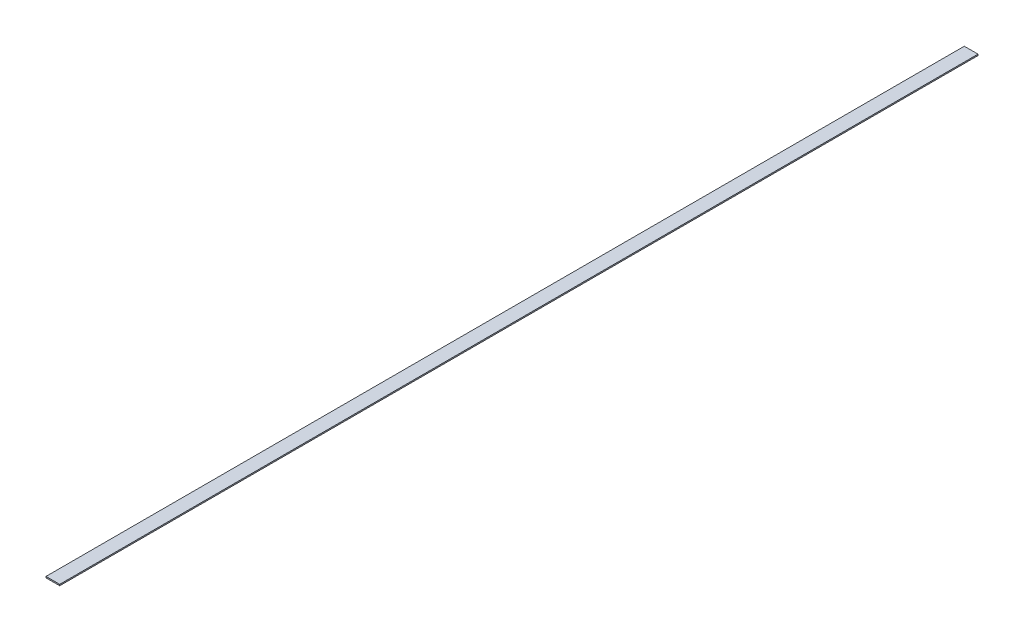
SolidWorks part; units mm, degrees
ref_plane "Front Plane" through (0, 0, 0) normal (0, 0, 1) x (1, 0, 0)
ref_plane "Top Plane" through (0, 0, 0) normal (0, 1, 0) x (1, 0, 0)
ref_plane "Right Plane" through (0, 0, 0) normal (1, 0, 0) x (0, 0, -1)
sketch "Sketch1" plane through (0, 0, 0) normal (0, 0, 1) x (1, 0, 0)
  line L1 (-44.4152, 29.4091) -> (6.3848, 29.4091)
  line L2 (-44.4152, 29.4091) -> (-44.4152, 24.6466)
  line L3 (-44.4152, 24.6466) -> (6.3848, 24.6466)
  line L4 (6.3848, 29.4091) -> (6.3848, 24.6466)
  dimension "D1" = 50.8
  dimension "D2" = 4.7625
extrude "Boss-Extrude1" add sketch "Sketch1" along normal blind 3403.6
